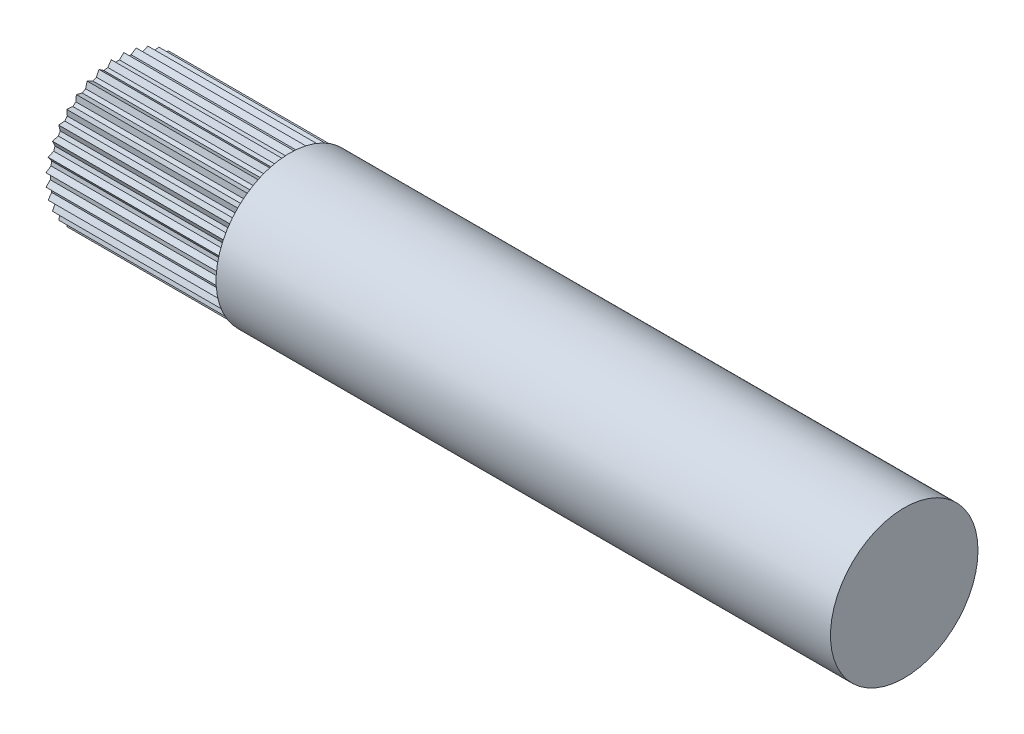
SolidWorks part; units mm, degrees
material "AISI 4130 Steel, annealed at 865C"
ref_plane "X-Y Datum" through (0, 0, 0) normal (0, 0, 1) x (1, 0, 0)
ref_plane "X-Z Datum" through (0, 0, 0) normal (0, 1, 0) x (1, 0, 0)
ref_plane "Y-Z Datum" through (0, 0, 0) normal (1, 0, 0) x (0, 0, -1)
sketch "Sketch1" plane through (0, 0, 0) normal (0, 1, 0) x (1, 0, 0)
  line L0 (139.925, 9.525) -> (139.925, 7.9375)
  line L1 (139.925, 7.9375) -> (19.25, 7.9375)
  line L2 (19.25, 7.9375) -> (19.25, 9.525)
  line L3 (19.25, 9.525) -> (139.925, 9.525)
  line L6 (157.324, 0) -> (-11.2643, 0) construction
  line L7 (19.25, 9.525) -> (19.25, -9.525) construction
  dimension "D1" = 1.5875
revolve "Revolve1" add sketch "Sketch1" angle 360 about L6
sketch "Sketch4" plane through (0, 0, 0) normal (1, 0, 0) x (0, 0, -1)
  line L0 (-9.2357, 0.808) -> (-8.6817, 0.254)
  line L1 (-8.6817, 0.254) -> (-8.6817, -0.254)
  line L2 (-8.6817, -0.254) -> (-9.2357, -0.808)
  line L3 (-8.6817, 0) -> (0, 0) construction
  line L4 (-8.5939, 1.2574) -> (-9.2357, 0.808)
  line L5 (-8.5057, 1.7577) -> (-8.5939, 1.2574)
  line L6 (-8.9551, 2.3995) -> (-8.5057, 1.7577)
  line L7 (-8.245, 2.7306) -> (-8.9551, 2.3995)
  line L8 (-8.0713, 3.208) -> (-8.245, 2.7306)
  line L9 (-8.4024, 3.9181) -> (-8.0713, 3.208)
  line L10 (-7.6456, 4.1209) -> (-8.4024, 3.9181)
  line L11 (-7.3916, 4.5608) -> (-7.6456, 4.1209)
  line L12 (-7.5944, 5.3176) -> (-7.3916, 4.5608)
  line L13 (-6.8138, 5.3859) -> (-7.5944, 5.3176)
  line L14 (-6.4873, 5.7751) -> (-6.8138, 5.3859)
  line L15 (-6.5556, 6.5556) -> (-6.4873, 5.7751)
  line L16 (-5.7751, 6.4873) -> (-6.5556, 6.5556)
  line L17 (-5.3859, 6.8138) -> (-5.7751, 6.4873)
  line L18 (-5.3176, 7.5944) -> (-5.3859, 6.8138)
  line L19 (-4.5608, 7.3916) -> (-5.3176, 7.5944)
  line L20 (-4.1209, 7.6456) -> (-4.5608, 7.3916)
  line L21 (-3.9181, 8.4024) -> (-4.1209, 7.6456)
  line L22 (-3.208, 8.0713) -> (-3.9181, 8.4024)
  line L23 (-2.7306, 8.245) -> (-3.208, 8.0713)
  line L24 (-2.3995, 8.9551) -> (-2.7306, 8.245)
  line L25 (-1.7577, 8.5057) -> (-2.3995, 8.9551)
  line L26 (-1.2574, 8.5939) -> (-1.7577, 8.5057)
  line L27 (-0.808, 9.2357) -> (-1.2574, 8.5939)
  line L28 (-0.254, 8.6817) -> (-0.808, 9.2357)
  line L29 (0.254, 8.6817) -> (-0.254, 8.6817)
  line L30 (0.808, 9.2357) -> (0.254, 8.6817)
  line L31 (1.2574, 8.5939) -> (0.808, 9.2357)
  line L32 (1.7577, 8.5057) -> (1.2574, 8.5939)
  line L33 (2.3995, 8.9551) -> (1.7577, 8.5057)
  line L34 (2.7306, 8.245) -> (2.3995, 8.9551)
  line L35 (3.208, 8.0713) -> (2.7306, 8.245)
  line L36 (3.9181, 8.4024) -> (3.208, 8.0713)
  line L37 (4.1209, 7.6456) -> (3.9181, 8.4024)
  line L38 (4.5608, 7.3916) -> (4.1209, 7.6456)
  line L39 (5.3176, 7.5944) -> (4.5608, 7.3916)
  line L40 (5.3859, 6.8138) -> (5.3176, 7.5944)
  line L41 (5.7751, 6.4873) -> (5.3859, 6.8138)
  line L42 (6.5556, 6.5556) -> (5.7751, 6.4873)
  line L43 (6.4873, 5.7751) -> (6.5556, 6.5556)
  line L44 (6.8138, 5.3859) -> (6.4873, 5.7751)
  line L45 (7.5944, 5.3176) -> (6.8138, 5.3859)
  line L46 (7.3916, 4.5608) -> (7.5944, 5.3176)
  line L47 (7.6456, 4.1209) -> (7.3916, 4.5608)
  line L48 (8.4024, 3.9181) -> (7.6456, 4.1209)
  line L49 (8.0713, 3.208) -> (8.4024, 3.9181)
  line L50 (8.245, 2.7306) -> (8.0713, 3.208)
  line L51 (8.9551, 2.3995) -> (8.245, 2.7306)
  line L52 (8.5057, 1.7577) -> (8.9551, 2.3995)
  line L53 (8.5939, 1.2574) -> (8.5057, 1.7577)
  line L54 (9.2357, 0.808) -> (8.5939, 1.2574)
  line L55 (8.6817, 0.254) -> (9.2357, 0.808)
  line L56 (8.6817, -0.254) -> (8.6817, 0.254)
  line L57 (9.2357, -0.808) -> (8.6817, -0.254)
  line L58 (8.5939, -1.2574) -> (9.2357, -0.808)
  line L59 (8.5057, -1.7577) -> (8.5939, -1.2574)
  line L60 (8.9551, -2.3995) -> (8.5057, -1.7577)
  line L61 (8.245, -2.7306) -> (8.9551, -2.3995)
  line L62 (8.0713, -3.208) -> (8.245, -2.7306)
  line L63 (8.4024, -3.9181) -> (8.0713, -3.208)
  line L64 (7.6456, -4.1209) -> (8.4024, -3.9181)
  line L65 (7.3916, -4.5608) -> (7.6456, -4.1209)
  line L66 (7.5944, -5.3176) -> (7.3916, -4.5608)
  line L67 (6.8138, -5.3859) -> (7.5944, -5.3176)
  line L68 (6.4873, -5.7751) -> (6.8138, -5.3859)
  line L69 (6.5556, -6.5556) -> (6.4873, -5.7751)
  line L70 (5.7751, -6.4873) -> (6.5556, -6.5556)
  line L71 (5.3859, -6.8138) -> (5.7751, -6.4873)
  line L72 (5.3176, -7.5944) -> (5.3859, -6.8138)
  line L73 (4.5608, -7.3916) -> (5.3176, -7.5944)
  line L74 (4.1209, -7.6456) -> (4.5608, -7.3916)
  line L75 (3.9181, -8.4024) -> (4.1209, -7.6456)
  line L76 (3.208, -8.0713) -> (3.9181, -8.4024)
  line L77 (2.7306, -8.245) -> (3.208, -8.0713)
  line L78 (2.3995, -8.9551) -> (2.7306, -8.245)
  line L79 (1.7577, -8.5057) -> (2.3995, -8.9551)
  line L80 (1.2574, -8.5939) -> (1.7577, -8.5057)
  line L81 (0.808, -9.2357) -> (1.2574, -8.5939)
  line L82 (0.254, -8.6817) -> (0.808, -9.2357)
  line L83 (-0.254, -8.6817) -> (0.254, -8.6817)
  line L84 (-0.808, -9.2357) -> (-0.254, -8.6817)
  line L85 (-1.2574, -8.5939) -> (-0.808, -9.2357)
  line L86 (-1.7577, -8.5057) -> (-1.2574, -8.5939)
  line L87 (-2.3995, -8.9551) -> (-1.7577, -8.5057)
  line L88 (-2.7306, -8.245) -> (-2.3995, -8.9551)
  line L89 (-3.208, -8.0713) -> (-2.7306, -8.245)
  line L90 (-3.9181, -8.4024) -> (-3.208, -8.0713)
  line L91 (-4.1209, -7.6456) -> (-3.9181, -8.4024)
  line L92 (-4.5608, -7.3916) -> (-4.1209, -7.6456)
  line L93 (-5.3176, -7.5944) -> (-4.5608, -7.3916)
  line L94 (-5.3859, -6.8138) -> (-5.3176, -7.5944)
  line L95 (-5.7751, -6.4873) -> (-5.3859, -6.8138)
  line L96 (-6.5556, -6.5556) -> (-5.7751, -6.4873)
  line L97 (-6.4873, -5.7751) -> (-6.5556, -6.5556)
  line L98 (-6.8138, -5.3859) -> (-6.4873, -5.7751)
  line L99 (-7.5944, -5.3176) -> (-6.8138, -5.3859)
  line L100 (-7.3916, -4.5608) -> (-7.5944, -5.3176)
  line L101 (-7.6456, -4.1209) -> (-7.3916, -4.5608)
  line L102 (-8.4024, -3.9181) -> (-7.6456, -4.1209)
  line L103 (-8.0713, -3.208) -> (-8.4024, -3.9181)
  line L104 (-8.245, -2.7306) -> (-8.0713, -3.208)
  line L105 (-8.9551, -2.3995) -> (-8.245, -2.7306)
  line L106 (-8.5057, -1.7577) -> (-8.9551, -2.3995)
  line L107 (-8.5939, -1.2574) -> (-8.5057, -1.7577)
  line L108 (-9.2357, -0.808) -> (-8.5939, -1.2574)
  circle A0 centre (0, 0) radius 8.6854 construction
  circle A1 centre (0, 0) radius 9.271 construction
  circle A2 centre (0, 0) radius 12.7
  point P155 (0, 0)
  dimension "D1" = 18.542
  dimension "D2" = 0.508
  dimension "D3" = 17.3708
  dimension "D6" = 25.4
  dimension "D4" = 135
  dimension "D5" = 1.616
  dimension "D7" = 36
sketch "Sketch6" plane through (19.25, 0, 0) normal (-1, 0, 0) x (0, 0, 1)
  circle A0 centre (0, 0) radius 7.9375
  dimension "D1" = 15.875
extrude "Boss-Extrude1" add sketch "Sketch6" against normal blind 101.6
sketch "Sketch7" plane through (120.85, 0, 0) normal (1, 0, 0) x (0, 0, -1)
  circle A0 centre (0, 0) radius 23.308
extrude "Cut-Extrude3" cut sketch "Sketch7" along normal up to surface (19.075 mm away) up to face at (139.925, 0, -9.525)
extrude "Cut-Extrude4" cut sketch "Sketch4" along normal blind 41.5011
